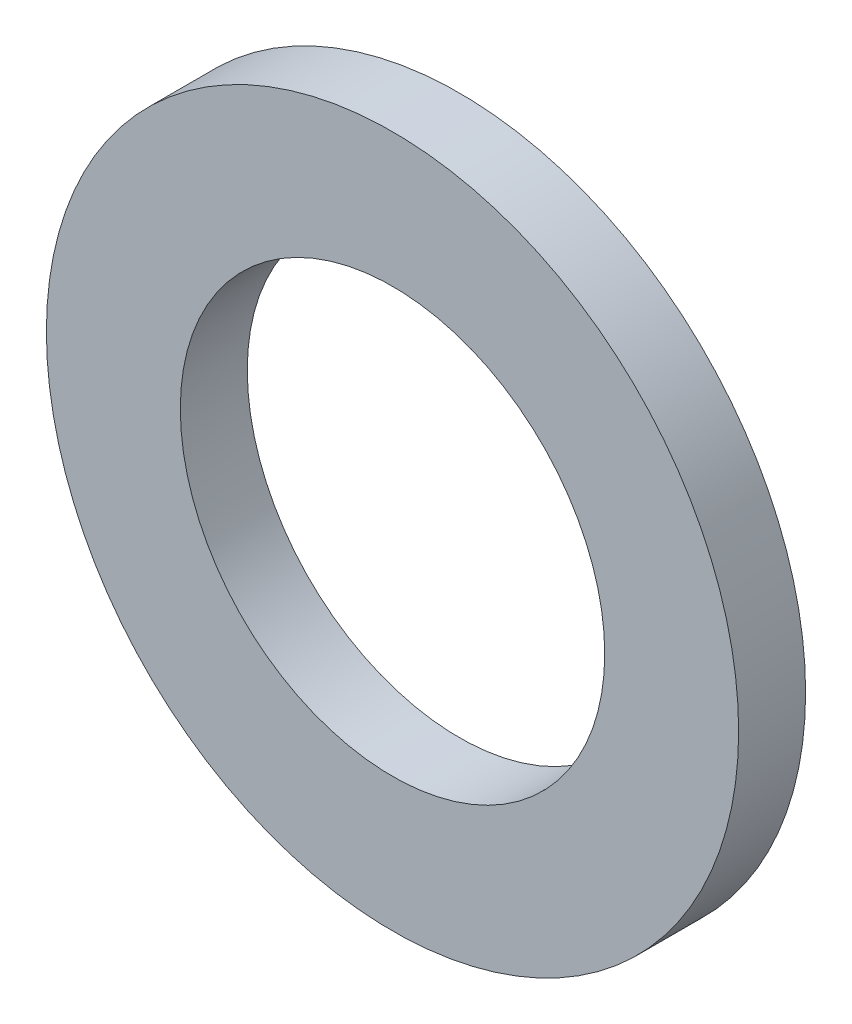
SolidWorks part; units mm, degrees
ref_plane "Front Plane" through (0, 0, 0) normal (0, 0, 1) x (1, 0, 0)
ref_plane "Top Plane" through (0, 0, 0) normal (0, 1, 0) x (1, 0, 0)
ref_plane "Right Plane" through (0, 0, 0) normal (1, 0, 0) x (0, 0, -1)
sketch "Sketch1" plane through (0, 0, 0) normal (0, 0, 1) x (1, 0, 0)
  circle A0 centre (0, 0) radius 4.025
  circle A1 centre (0, 0) radius 6.565
  dimension "D1" = 8.05
  dimension "D2" = 2.54
extrude "Boss-Extrude1" add sketch "Sketch1" along normal blind 1.27
